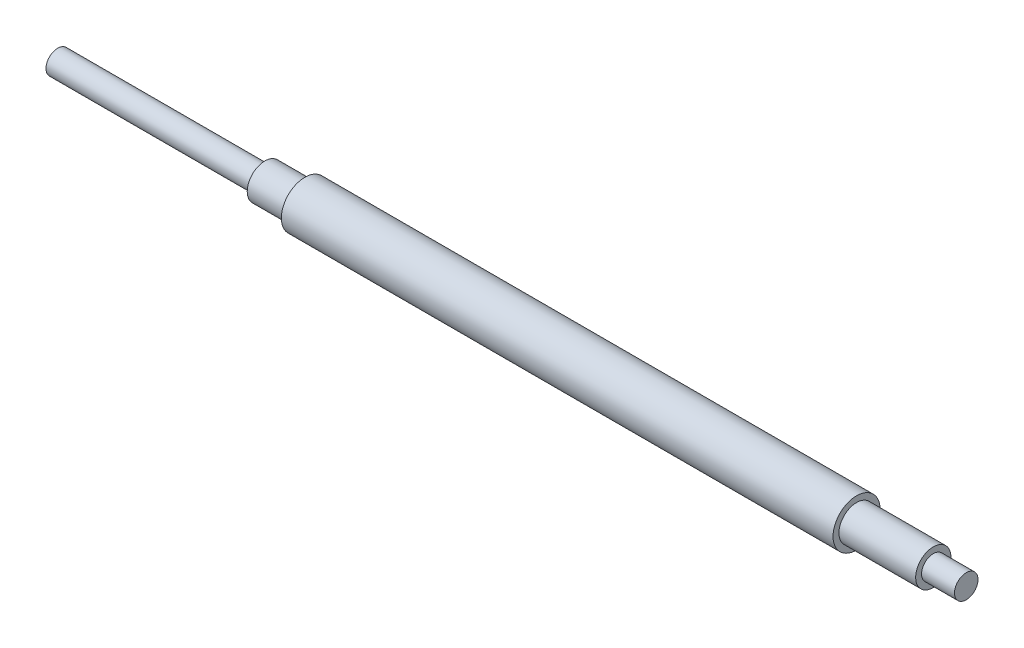
SolidWorks part; units mm, degrees
ref_plane "Front Plane" through (0, 0, 0) normal (0, 0, 1) x (1, 0, 0)
ref_plane "Top Plane" through (0, 0, 0) normal (0, 1, 0) x (1, 0, 0)
ref_plane "Right Plane" through (0, 0, 0) normal (1, 0, 0) x (0, 0, -1)
sketch "Sketch1" plane through (0, 0, 0) normal (0, 0, 1) x (1, 0, 0)
  line L3 (-12.9766, 3.175) -> (-12.9766, 0)
  line L4 (-12.9766, 3.175) -> (-21.8666, 3.175)
  line L5 (-21.8666, 3.175) -> (-21.8666, 4.7625)
  line L6 (-21.8666, 4.7625) -> (-42.5676, 4.7625)
  line L7 (-42.5676, 4.7625) -> (-42.5676, 6.35)
  line L8 (-42.5676, 6.35) -> (-191.4116, 6.35)
  line L9 (-191.4116, 6.35) -> (-191.4116, 4.7625)
  line L10 (-191.4116, 4.7625) -> (-202.2066, 4.7625)
  line L11 (-202.2066, 4.7625) -> (-202.2066, 3.175)
  line L12 (-202.2066, 3.175) -> (-258.0866, 3.175)
  line L13 (-258.0866, 3.175) -> (-258.0866, 0)
  line L14 (-258.0866, 0) -> (-12.9766, 0)
  line L16 (-191.4116, -5.0403) -> (-191.4116, 5.0403) construction
  line L18 (0, 0) -> (27.519, 0) construction
  line L19 (-253.0066, 10.16) -> (-253.0066, -10.16) construction
  dimension "D1" = 6.35
  dimension "D3" = 4.7625
  dimension "D4" = 3.175
  dimension ".35" = 8.89
  dimension "D6" = 3.175
  dimension "D7" = 148.844
  dimension "D8" = 10.795
  dimension "D9" = 5.08
  dimension "D2" = 20.701
revolve "Revolve1" add sketch "Sketch1" angle 360 about L14
equation "\"CompressorInnerDiameter\"=0.125"
equation "\"D4@Sketch1\"=\"CompressorInnerDiameter\""
